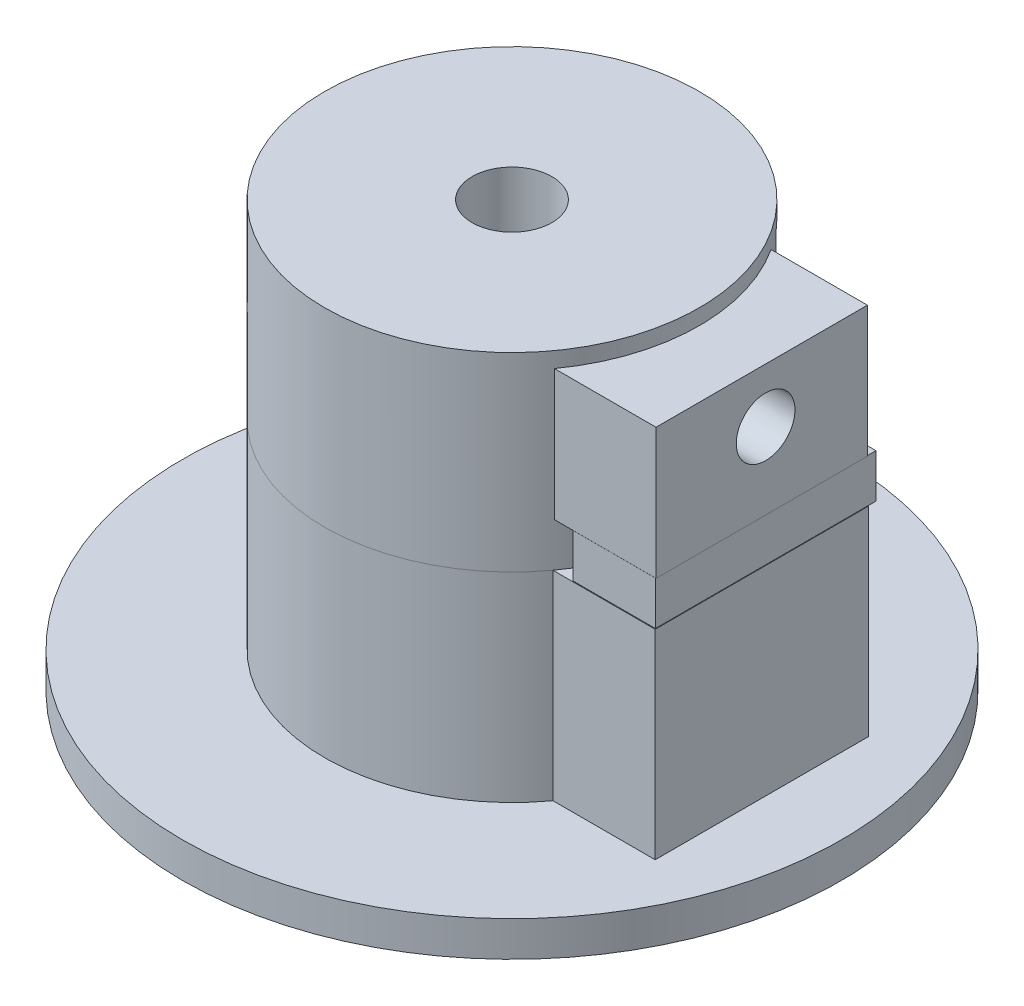
SolidWorks part; units mm, degrees
ref_plane "Front Plane" through (0, 0, 0) normal (0, 0, 1) x (1, 0, 0)
ref_plane "Top Plane" through (0, 0, 0) normal (0, 1, 0) x (1, 0, 0)
ref_plane "Right Plane" through (0, 0, 0) normal (1, 0, 0) x (0, 0, -1)
sketch "Sketch1" plane through (0, 0, 0) normal (0, 1, 0) x (1, 0, 0)
  circle A0 centre (0, 0) radius 15.958
  point P3 (0, 0)
extrude "ShaftHolderNearMotor" add sketch "Sketch1" along normal blind 17.19
sketch "Sketch2" plane through (0, 17.19, 0) normal (0, 1, 0) x (1, 0, 0)
  circle A0 centre (0, 0) radius 3.4
extrude "ShaftHole" cut sketch "Sketch2" against normal blind 16.85 contours A0
ref_plane "Plane1" through (0, 12.15, 0) normal (0, 1, 0) x (1, 0, 0)
ref_axis "Axis1" through (0, -74.793, 0) along (0, 1, 0)
ref_point "Point2"
sketch "Sketch5" plane through (0, 12.15, 0) normal (0, 1, 0) x (1, 0, 0)
  line L0 (0, 0) -> (2.6, 0) construction
  line L2 (2.6, -3.5716) -> (4.1507, -3.5716)
  line L3 (2.6, -3.5716) -> (2.6, 3.6126)
  line L4 (2.6, 3.6126) -> (4.1507, 3.6126)
  line L5 (4.1507, -3.5716) -> (4.1507, 3.6126)
extrude "Boss-Extrude2" add sketch "Sketch5" against normal blind 13.55
sketch "Sketch7" plane through (2.6, 0, 0) normal (-1, 0, 0) x (0, 0, 1)
  line L1 (-8.6717, 14.8677) -> (9.3323, 14.8677)
  line L2 (-8.6717, 14.8677) -> (-8.6717, 3.7227)
  line L3 (-8.6717, 3.7227) -> (9.3323, 3.7227)
  line L4 (9.3323, 14.8677) -> (9.3323, 3.7227)
extrude "Boss-Extrude3" add sketch "Sketch7" against normal blind 19
sketch "Sketch6" plane through (2.6, 0, 0) normal (-1, 0, 0) x (0, 0, 1)
  line L1 (-2.1909, 0.34) -> (-2.1909, 14.8677) construction
  line L2 (2.1909, 14.8677) -> (2.1909, 0.34) construction
  line L3 (-2.1909, 15.4522) -> (2.1909, 15.4522) construction
  circle A0 centre (0, 10.2369) radius 2.5
extrude "BoltHole" cut sketch "Sketch6" against normal up to surface (19 mm away) and the other way blind 1 up to face at (21.6, 9.2952, 0.3303)
ref_axis "Axis2" through (-1.8994, 10.2369, 0) along (-1, 0, 0)
ref_axis "Axis4" through (21.6, 10.2369, 0) along (-1, 0, 0)
ref_plane "Plane3" through (0, 0, 0) normal (0, 0, 1) x (1, 0, 0)
sketch "Sketch10" plane through (0, 0, 0) normal (0, -1, 0) x (1, 0, 0)
  circle A0 centre (0, 0) radius 50
extrude "Boss-Extrude4" add sketch "Sketch10" along normal blind 20
sketch "Sketch11" plane through (0, 0, 0) normal (0, 1, 0) x (1, 0, 0)
  line L1 (31.7817, 38.8528) -> (14.4942, 48.0577) construction
  line L2 (14.4942, 48.0577) -> (-5, 49.9462) construction
  line L3 (-5, 49.9462) -> (-23.733, 44.2308) construction
  line L4 (-23.733, 44.2308) -> (-38.8528, 31.7817) construction
  line L5 (-38.8528, 31.7817) -> (-48.0577, 14.4942) construction
  line L6 (-48.0577, 14.4942) -> (-49.9462, -5) construction
  line L7 (-49.9462, -5) -> (-44.2308, -23.733) construction
  line L8 (-44.2308, -23.733) -> (-31.7817, -38.8528) construction
  line L9 (-31.7817, -38.8528) -> (-14.4942, -48.0577) construction
  line L10 (-14.4942, -48.0577) -> (5, -49.9462) construction
  line L11 (5, -49.9462) -> (23.733, -44.2308) construction
  line L12 (23.733, -44.2308) -> (38.8528, -31.7817) construction
  line L13 (38.8528, -31.7817) -> (48.0577, -14.4942) construction
  line L14 (48.0577, -14.4942) -> (49.9462, 5) construction
  line L15 (49.9462, 5) -> (44.2308, 23.733) construction
  line L16 (44.2308, 23.733) -> (31.7817, 38.8528) construction
  circle A0 centre (0, 0) radius 49.2313 construction
  circle A1 centre (5, -49.9462) radius 5
  circle A2 centre (-14.4942, -48.0577) radius 5
  circle A3 centre (-31.7817, -38.8528) radius 5
  circle A4 centre (-44.2308, -23.733) radius 5
  circle A5 centre (-49.9462, -5) radius 5
  circle A6 centre (-48.0577, 14.4942) radius 5
  circle A7 centre (-38.8528, 31.7817) radius 5
  circle A8 centre (-23.733, 44.2308) radius 5
  circle A9 centre (-5, 49.9462) radius 5
  circle A10 centre (14.4942, 48.0577) radius 5
  circle A11 centre (31.7817, 38.8528) radius 5
  circle A12 centre (44.2308, 23.733) radius 5
  circle A13 centre (49.9462, 5) radius 5
  circle A14 centre (48.0577, -14.4942) radius 5
  circle A15 centre (38.8528, -31.7817) radius 5
  circle A16 centre (23.733, -44.2308) radius 5
sketch "Sketch12" plane through (0, 0, 0) normal (0, 1, 0) x (1, 0, 0)
  circle A0 centre (0, 0) radius 43
  circle A1 centre (0, 0) radius 15.9579
extrude "CutToRemveExcessMaterial" cut sketch "Sketch12" against normal offset from surface (17 mm away) 3 up to face at (0, -20, -50)
sketch "Sketch13" plane through (0, 0, 0) normal (0, 1, 0) x (1, 0, 0)
  circle A0 centre (0, 0) radius 42.6967
  circle A1 centre (0, 0) radius 50
extrude "Boss-Extrude5" add sketch "Sketch13" along normal blind 17
sketch "Sketch9" plane through (0, 0, 0) normal (0, 0, 1) x (1, 0, 0)
  line L0 (11.8765, 10.2369) -> (11.8765, 5.9284) construction
  line L1 (4.9434, 5.9284) -> (11.8765, 5.9284) construction
  line L2 (4.9434, 5.9284) -> (4.9434, 10.2369) construction
  line L3 (4.9434, 10.2369) -> (4.9434, 14.4709) construction
  line L4 (4.9434, 14.4709) -> (11.8765, 14.4709) construction
  line L5 (11.8765, 14.4709) -> (11.8765, 10.2369) construction
  line L6 (21.6, 10.2369) -> (2.1647, 10.2369) construction
  line L7 (4.9434, 14.4709) -> (11.8765, 5.9284) construction
  line L8 (4.9434, 14.4709) -> (2.2275, 17.8172) construction
  line L9 (11.8765, 5.9284) -> (13.8816, 3.4579) construction
  line L11 (4.6498, 14.8327) -> (12.177, 14.8327) construction
  line L12 (4.6498, 14.8327) -> (4.6498, 5.5583) construction
  line L13 (4.6498, 5.5583) -> (12.177, 5.5583) construction
  line L14 (12.177, 14.8327) -> (12.177, 5.5583) construction
  line L15 (4.6769, 14.7993) -> (12.1392, 14.7993)
  line L16 (4.6769, 14.7993) -> (4.6769, 5.6048)
  line L17 (4.6769, 5.6048) -> (12.1392, 5.6048)
  line L18 (12.1392, 14.7993) -> (12.1392, 5.6048)
  circle A0 centre (4.9434, 14.4709) radius 0.466 construction
  circle A1 centre (11.8765, 5.9284) radius 0.4768 construction
  circle A2 centre (4.9434, 14.4709) radius 0.423 construction
  circle A3 centre (11.8765, 5.9284) radius 0.423 construction
  point P22 (4.8945, 14.5691)
  point P23 (4.8835, 14.5488)
  point P24 (0, 0)
  point P25 (11.9443, 5.7778)
  point P26 (11.9547, 5.7622)
  point P27 (4.865, 14.5686)
  point P28 (11.9536, 5.7107)
  point P29 (4.8665, 14.567)
  point P30 (12.1392, 5.6048)
  point P31 (4.6769, 14.7993)
extrude "NutOpening" cut sketch "Sketch9" against normal through all
sketch "Sketch14" plane through (12.1392, 0, 0) normal (-1, 0, 0) x (0, 0, 1)
  line L1 (-5.3208, 10.2369) -> (-2.6604, 5.629)
  line L2 (-2.6604, 5.629) -> (2.6604, 5.629)
  line L3 (2.6604, 5.629) -> (5.3208, 10.2369)
  line L4 (5.3208, 10.2369) -> (2.6604, 14.8449)
  line L5 (2.6604, 14.8449) -> (-2.6604, 14.8449)
  line L6 (-2.6604, 14.8449) -> (-5.3208, 10.2369)
  circle A0 centre (0, 10.2369) radius 4.608 construction
extrude "HexCut" cut sketch "Sketch14" along normal up to surface (7.4623 mm away) up to face at (4.6769, 10.2137, -5.5024)
sketch "Sketch16" plane through (21.6, 0, 0) normal (1, 0, 0) x (0, 0, -1)
  circle A0 centre (0, 10.2369) radius 6
extrude "Cut-Extrude7" cut sketch "Sketch16" along normal blind 40
ref_plane "Plane4" through (-0.571, 0, -49.9967) normal (-0.0114, 0, -0.9999) x (-0.9999, 0, 0.0114)
ref_plane "Plane5" through (-27.4359, 0, -41.8004) normal (-0.5487, 0, -0.836) x (-0.836, 0, 0.5487)
sketch "Sketch17" plane through (-0.571, 0, -49.9967) normal (-0.0114, 0, -0.9999) x (-0.9999, 0, 0.0114)
  line L1 (-6.9779, 26.3682) -> (19.0025, 26.3682)
sketch "Sketch18" plane through (-27.4359, 0, -41.8004) normal (-0.5487, 0, -0.836) x (-0.836, 0, 0.5487)
  line L1 (2.3429, -8.8145) -> (-7.3736, -8.8145)
  line L2 (2.3429, -8.8145) -> (2.3429, -36.514)
  line L3 (2.3429, -36.514) -> (-7.3736, -36.514)
  line L4 (-7.3736, -8.8145) -> (-7.3736, -36.514)
ref_plane "Plane6" through (18.6054, 0, -46.4095) normal (0.3721, 0, -0.9282) x (-0.9282, 0, -0.3721)
ref_plane "Plane7" through (34.9493, 0, -35.7568) normal (0.699, 0, -0.7151) x (-0.7151, 0, -0.699)
ref_plane "Plane8" through (45.9725, 0, -19.6605) normal (0.9194, 0, -0.3932) x (-0.3932, 0, -0.9194)
ref_plane "Plane9" through (49.1178, 0, -9.3511) normal (0.9824, 0, -0.187) x (-0.187, 0, -0.9824)
ref_plane "Plane10" through (46.4095, 0, 18.6054) normal (0.9282, 0, 0.3721) x (0.3721, 0, -0.9282)
ref_plane "Plane11" through (35.7568, 0, 34.9493) normal (0.7151, 0, 0.699) x (0.699, 0, -0.7151)
ref_plane "Plane12" through (9.3511, 0, 49.1178) normal (0.187, 0, 0.9824) x (0.9824, 0, -0.187)
ref_plane "Plane13" through (-28.1193, 0, 41.3438) normal (-0.5624, 0, 0.8269) x (0.8269, 0, 0.5624)
ref_plane "Plane14" through (-49.1178, 0, 9.3511) normal (-0.9824, 0, 0.187) x (0.187, 0, 0.9824)
ref_plane "Plane15" through (-41.3438, 0, -28.1193) normal (-0.8269, 0, -0.5624) x (-0.5624, 0, 0.8269)
sketch "Sketch19" plane through (9.3511, 0, 49.1178) normal (0.187, 0, 0.9824) x (0.9824, 0, -0.187)
  circle A0 centre (-6.5538, -15.0444) radius 12
extrude "Cut-Extrude8" cut sketch "Sketch19" against normal blind 5
sketch "Sketch20" plane through (35.7568, 0, 34.9493) normal (0.7151, 0, 0.699) x (0.699, 0, -0.7151)
  circle A0 centre (3.5584, 19.4292) radius 12
extrude "Cut-Extrude9" cut sketch "Sketch20" against normal blind 5
sketch "Sketch21" plane through (49.1178, 0, -9.3511) normal (0.9824, 0, -0.187) x (-0.187, 0, -0.9824)
  circle A0 centre (-4.7912, -19.2219) radius 10
sketch "Sketch22" plane through (34.9493, 0, -35.7568) normal (0.699, 0, -0.7151) x (-0.7151, 0, -0.699)
  circle A0 centre (5.4277, 18.4908) radius 12.5535
extrude "Cut-Extrude10" cut sketch "Sketch22" against normal blind 5
extrude "Cut-Extrude11" cut sketch "Sketch21" against normal blind 5 contours A0
sketch "Sketch23" plane through (-0.571, 0, -49.9967) normal (-0.0114, 0, -0.9999) x (-0.9999, 0, 0.0114)
  circle A0 centre (4.5252, -20.0178) radius 11.9653
extrude "Cut-Extrude12" cut sketch "Sketch23" against normal blind 5
sketch "Sketch25" plane through (-41.3438, 0, -28.1193) normal (-0.8269, 0, -0.5624) x (-0.5624, 0, 0.8269)
  circle A0 centre (-2.6498, 18.6432) radius 9.6297
extrude "Cut-Extrude13" cut sketch "Sketch25" against normal blind 5
sketch "Sketch26" plane through (-49.1178, 0, 9.3511) normal (-0.9824, 0, 0.187) x (0.187, 0, 0.9824)
  circle A0 centre (-4.4977, -19.1264) radius 15.0124
extrude "Cut-Extrude14" cut sketch "Sketch26" against normal blind 5
sketch "Sketch27" plane through (-28.1193, 0, 41.3438) normal (-0.5624, 0, 0.8269) x (0.8269, 0, 0.5624)
  circle A0 centre (-2.2875, 17.6222) radius 11.8547
extrude "Cut-Extrude15" cut sketch "Sketch27" against normal blind 5
sketch "Sketch28" plane through (0, 0, 0) normal (0, -1, 0) x (1, 0, 0)
  line L1 (12.7613, 9.4042) -> (21.6, 9.4042)
  line L2 (12.7613, 9.4042) -> (12.7613, -8.7683)
  line L3 (12.7613, -8.7683) -> (21.6, -8.7683)
  line L4 (21.6, 9.4042) -> (21.6, -8.7683)
extrude "Boss-Extrude6" add sketch "Sketch28" along normal up to surface (17 mm away) up to face at (0, -17, -43)
sketch "Sketch29" plane through (0, 3.7227, 0) normal (0, -1, 0) x (1, 0, 0)
  line L1 (21.5487, 9.3378) -> (14.5231, 9.3378)
  line L2 (21.5487, 9.3378) -> (21.5487, -9.4483)
  line L3 (21.5487, -9.4483) -> (14.5231, -9.4483)
  line L4 (14.5231, 9.3378) -> (14.5231, -9.4483)
extrude "Boss-Extrude7" add sketch "Sketch29" along normal up to surface (3.7227 mm away) up to face at (18.0666, 0, 0.3352)
sketch "Sketch30" plane through (0, 17.19, 0) normal (0, 1, 0) x (1, 0, 0)
  circle A0 centre (0, 0) radius 3.4
  circle A1 centre (0, 0) radius 8.7876
sketch "Sketch31" plane through (0, 17.19, 0) normal (0, 1, 0) x (1, 0, 0)
  circle A0 centre (0, 0) radius 26.3365
extrude "Cut-Extrude16" cut sketch "Sketch31" against normal blind 1
sketch "Sketch32" plane through (0, 14.8677, 0) normal (0, 1, 0) x (1, 0, 0)
  circle A0 centre (0, 0) radius 3.3803
extrude "Cut-Extrude17" cut sketch "Sketch32" against normal blind 2
ref_point "Point4"
sketch "Sketch33" plane through (0, -20, 0) normal (0, -1, 0) x (1, 0, 0)
  circle A0 centre (0, 0) radius 28.0686
  circle A1 centre (0, 0) radius 63.3241
extrude "RemoveOutsideOfWheel(WouldLikeToDisableThis)" cut sketch "Sketch33" against normal through all
sketch "Sketch37" plane through (4.6769, 0, 0) normal (1, 0, 0) x (0, 0, -1)
  line L0 (15.2573, 5.6048) -> (14.3236, 3.3685)
  line L1 (14.3236, 3.3685) -> (5.9217, 5.6048)
  line L2 (15.2573, 5.6048) -> (0, 5.6048) construction
  line L3 (5.9217, 5.6048) -> (15.2573, 5.6048)
  point P6 (5.9217, 5.7107)
extrude "CutOutWedgeToMakeBotInsertionEasier" cut sketch "Sketch37" along normal up to surface (7.4623 mm away) up to face at (12.1392, 10.2214, -1.7136)
